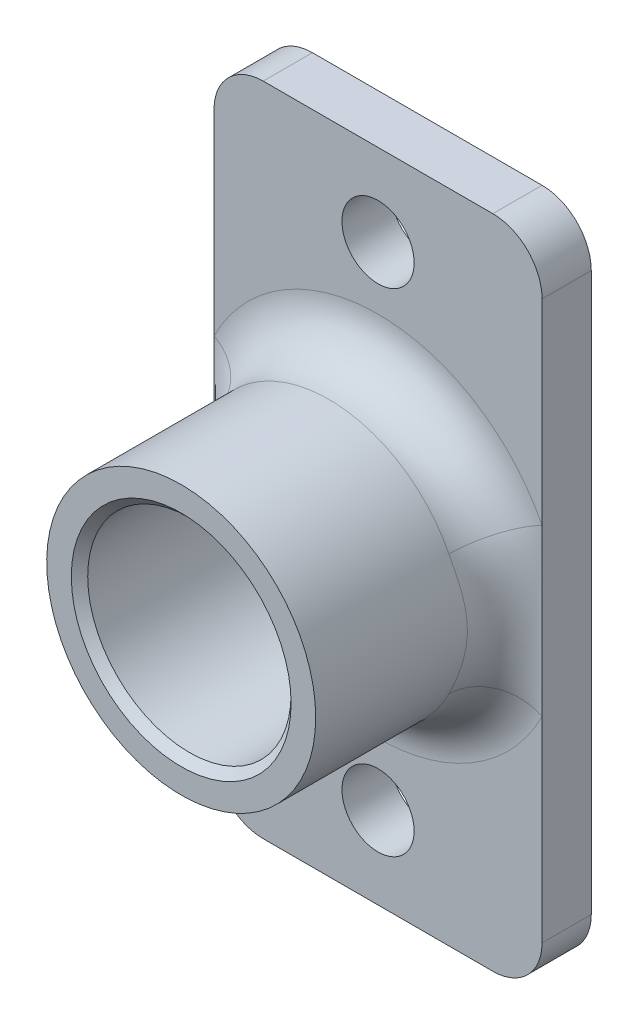
SolidWorks part; units mm, degrees
material "ABS"
ref_plane "Front Plane" through (0, 0, 0) normal (0, 0, 1) x (1, 0, 0)
ref_plane "Top Plane" through (0, 0, 0) normal (0, 1, 0) x (1, 0, 0)
ref_plane "Right Plane" through (0, 0, 0) normal (1, 0, 0) x (0, 0, -1)
sketch "Sketch1" plane through (0, 0, 0) normal (0, 0, 1) x (1, 0, 0)
  line L1 (-10, -20) -> (10, -20)
  line L2 (-10, -20) -> (-10, 20)
  line L3 (-10, 20) -> (10, 20)
  line L4 (10, -20) -> (10, 20)
  line L5 (-10, -20) -> (10, 20) construction
  line L6 (-10, 20) -> (10, -20) construction
  point P0 (0, 0)
  dimension "D1" = 20
  dimension "D2" = 40
extrude "Boss-Extrude1" add sketch "Sketch1" along normal blind 3
sketch "Sketch2" plane through (0, 0, 3) normal (0, 0, 1) x (1, 0, 0)
  circle A0 centre (0, 0) radius 8.2
  dimension "D1" = 16.4
extrude "Boss-Extrude2" add sketch "Sketch2" along normal blind 12
sketch "Sketch3" plane through (0, 0, 15) normal (0, 0, 1) x (1, 0, 0)
  circle A0 centre (0, 0) radius 6.2
  dimension "D1" = 12.4
extrude "Cut-Extrude1" cut sketch "Sketch3" against normal through all
sketch "Sketch4" plane through (0, 0, 3) normal (0, 0, 1) x (1, 0, 0)
  line L0 (0, 15) -> (0, -15) construction
  circle A0 centre (0, 15) radius 2.2
  circle A1 centre (0, -15) radius 2.2
  dimension "D1" = 4.4
  dimension "D2" = 30
extrude "Cut-Extrude2" cut sketch "Sketch4" against normal through all
chamfer "Chamfer2" distance 0.5 angle 45 1 edges at (6.2, 0, 15)
fillet "Fillet1" radius 3 4 edges at (-10, -20, 1.5) (10, -20, 1.5) (10, 20, 1.5) (-10, 20, 1.5)
fillet "Fillet2" radius 3 1 edges at (-8.2, 0, 3)
